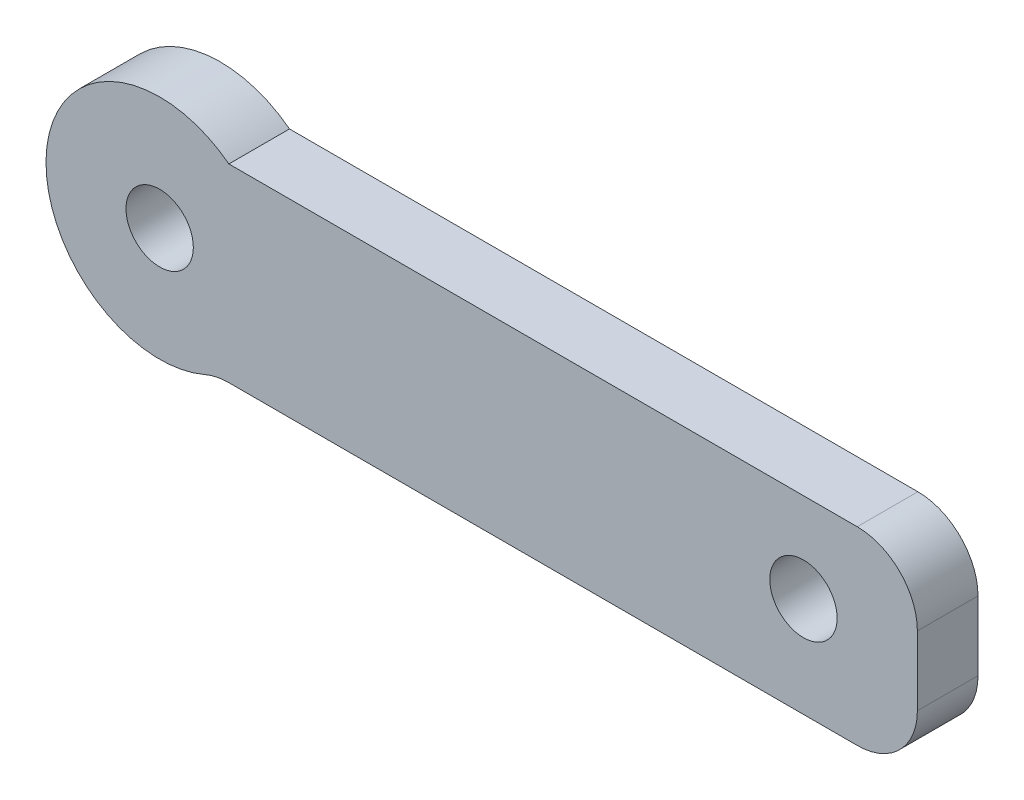
SolidWorks part; units mm, degrees
material "6061-T4 (SS)"
ref_plane "Front Plane" through (0, 0, 0) normal (0, 0, 1) x (1, 0, 0)
ref_plane "Top Plane" through (0, 0, 0) normal (0, 1, 0) x (1, 0, 0)
ref_plane "Right Plane" through (0, 0, 0) normal (1, 0, 0) x (0, 0, -1)
sketch "Sketch1" plane through (0, 0, 0) normal (0, 0, 1) x (1, 0, 0)
  line L1 (1.827, -2.6205) -> (18.4125, -2.6205)
  line L3 (1.827, 2.3795) -> (18.4125, 2.3795)
  line L4 (20, -1.033) -> (20, 0.792)
  arc A0 (1.827, 2.3795) -> (1.1948, -2.7518) centre (0, 0) ccw
  arc A1 (1.827, -2.6205) -> (1.1948, -2.7518) centre (1.827, -4.208) ccw
  arc A3 (18.4125, -2.6205) -> (20, -1.033) centre (18.4125, -1.033) ccw
  arc A4 (18.4125, 2.3795) -> (20, 0.792) centre (18.4125, 0.792) cw
  point P12 (20, -2.6205)
  point P15 (20, 2.3795)
  dimension "D2" = 6
  dimension "D4" = 1.5875
  dimension "D5" = 1.5875
  dimension "D1" = 20
  dimension "D3" = 5
extrude "Boss-Extrude1" add sketch "Sketch1" along normal blind 1.6002
hole_wizard "#0 Clearance Hole1" positions "Sketch2" profile "Sketch3" hole size "#0" standard "ANSI Inch"
sketch "Sketch2" plane through (0, 0, 1.6002) normal (0, 0, 1) x (1, 0, 0)
  arc A0 (1.827, 2.3795) -> (1.1948, -2.7518) centre (0, 0) ccw construction
  point P0 (0, 0)
  point P3 (0, 0)
sketch "Sketch3" plane through (0, 0, 1.6002) normal (1, 0, 0) x (0, -1, 0)
  line L0 (0, 0) -> (0, 465.5342)
  line L1 (0, 465.5342) -> (0.889, 465)
  line L2 (0.889, 465) -> (0.889, 0)
  line L5 (0.889, 0) -> (0, 0)
  line L10 (0, 465.5342) -> (-0.889, 465) construction
  line L11 (0, -6.35) -> (0, 107.95) construction
  dimension "Hole Dia." = 1.778
  dimension "Hole Depth" = 465
  dimension "Drill Angle" = 118
sketch "Sketch7" plane through (0, 0, 0) normal (0, 0, -1) x (-1, 0, 0)
  line L0 (-8.6344, 0) -> (0, 0)
  point P3 (-8.6344, 0)
sketch "Sketch8" plane through (0, 0, 1.6002) normal (0, 0, 1) x (1, 0, 0)
  line L0 (0, -16.9706) -> (16.9932, 0.0227) construction
  line L1 (8.6344, 0) -> (0, 0) construction
  point P3 (17.0158, 0)
  dimension "D1" = 45
hole_wizard "#0 Clearance Hole2" positions "Sketch9" profile "Sketch10" hole size "#0" standard "ANSI Inch"
sketch "Sketch9" plane through (0, 0, 0) normal (0, 0, -1) x (-1, 0, 0)
  point P0 (-16.9932, 0.0227)
  point P3 (-16.954, 0)
sketch "Sketch10" plane through (16.9932, 0.0227, 0) normal (1, 0, 0) x (0, 1, 0)
  line L0 (0, 0) -> (0, 465.5342)
  line L1 (0, 465.5342) -> (0.889, 465)
  line L2 (0.889, 465) -> (0.889, 0)
  line L5 (0.889, 0) -> (0, 0)
  line L10 (0, 465.5342) -> (-0.889, 465) construction
  line L11 (0, -6.35) -> (0, 107.95) construction
  dimension "Hole Dia." = 1.778
  dimension "Hole Depth" = 465
  dimension "Drill Angle" = 118
